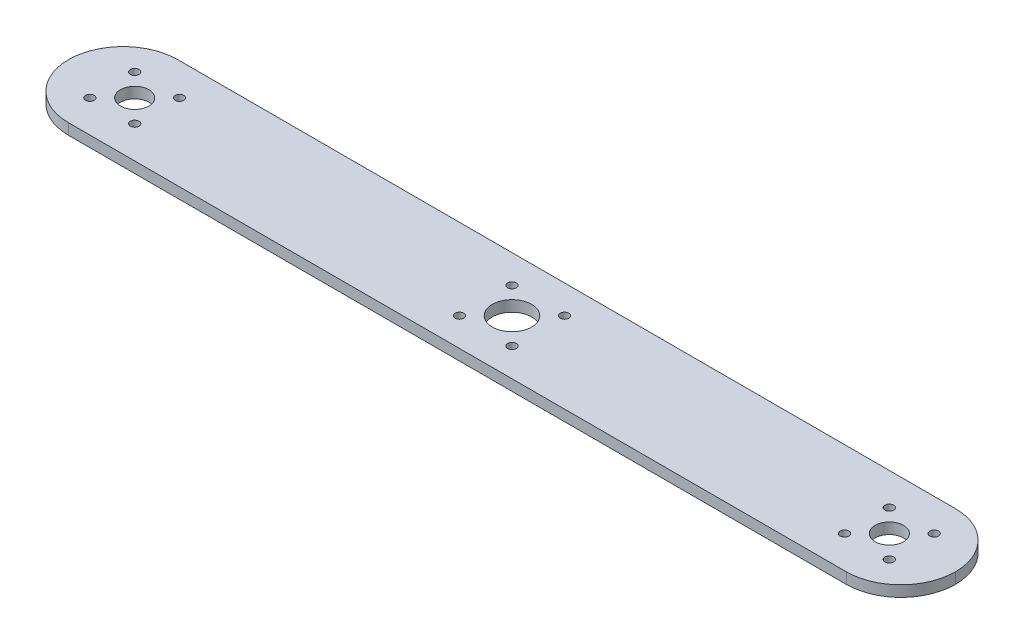
SolidWorks part; units mm, degrees
material "2014 合金"
ref_plane "正面" through (0, 0, 0) normal (0, 0, 1) x (1, 0, 0)
ref_plane "平面" through (0, 0, 0) normal (0, 1, 0) x (1, 0, 0)
ref_plane "右側面" through (0, 0, 0) normal (1, 0, 0) x (0, 0, -1)
sketch "ｽｹｯﾁ1" plane through (0, 0, 0) normal (0, 1, 0) x (1, 0, 0)
  line L0 (-172.7, 0) -> (172.7, 0)
  line L1 (0, 25) -> (0, -25) construction
  line L2 (0, -17) -> (0, 17)
  line L3 (172.7, -14.5) -> (172.7, 14.5)
  line L5 (-203, 25) -> (203, 25)
  line L6 (-203, 25) -> (-203, -25)
  line L7 (-203, -25) -> (203, -25)
  line L8 (203, 25) -> (203, -25)
  line L9 (-203, 25) -> (203, -25) construction
  line L10 (-203, -25) -> (203, 25) construction
  circle A0 centre (172.7, 0) radius 6.5
  circle A1 centre (-172.7, 0) radius 6.5
  circle A2 centre (0, 0) radius 9
  circle A4 centre (12.0208, 12.0208) radius 2
  circle A6 centre (12.0208, -12.0208) radius 2
  circle A7 centre (-182.953, 10.253) radius 2
  circle A8 centre (182.953, 10.253) radius 2
  circle A9 centre (-182.953, -10.253) radius 2
  circle A10 centre (182.953, -10.253) radius 2
  circle A11 centre (-162.447, -10.253) radius 2
  circle A12 centre (-162.447, 10.253) radius 2
  circle A14 centre (-12.0208, -12.0208) radius 2
  circle A16 centre (162.447, -10.253) radius 2
  circle A17 centre (-12.0208, 12.0208) radius 2
  circle A18 centre (162.447, 10.253) radius 2
  point P3 (0, 0)
  point P4 (0, 0)
  point P18 (0, 0)
  point P28 (0, 0)
  point P29 (172.7, 0)
  point P39 (172.7, 0)
  dimension "D4" = 13
  dimension "D5" = 18
  dimension "D1" = 345.4
  dimension "D2" = 406
  dimension "D3" = 50
  dimension "D6" = 34
extrude "ﾎﾞｽ - 押し出し1" add sketch "ｽｹｯﾁ1" along normal blind 5 contours L8 L5 L6 L7 region at (0, 0, -20.9093)
fillet "ﾌｨﾚｯﾄ1" radius 25 4 edges at (-203, 2.5, -25) (-203, 2.5, 25) (203, 2.5, 25) (203, 2.5, -25)
